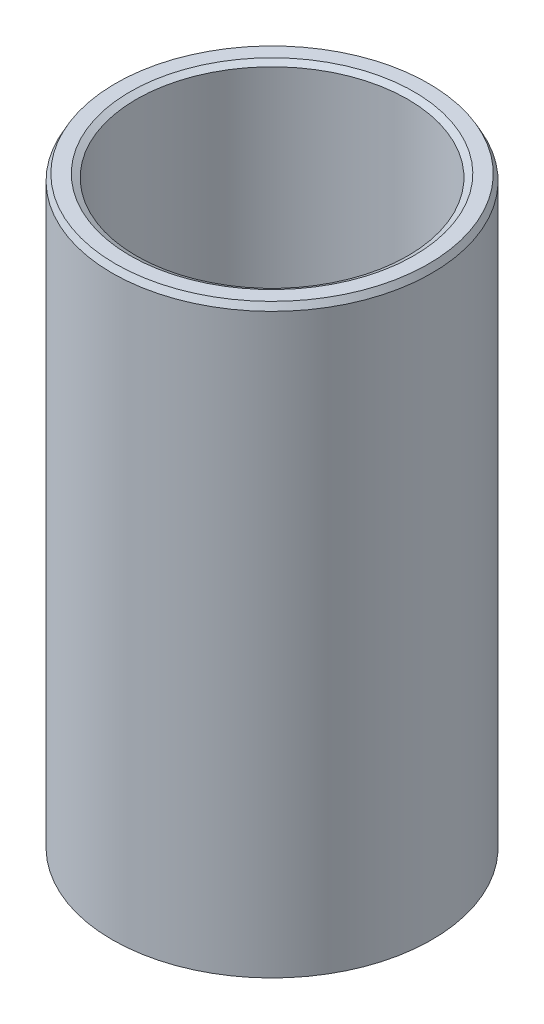
SolidWorks part; units mm, degrees
ref_plane "Front Plane" through (0, 0, 0) normal (0, 0, 1) x (1, 0, 0)
ref_plane "Top Plane" through (0, 0, 0) normal (0, 1, 0) x (1, 0, 0)
ref_plane "Right Plane" through (0, 0, 0) normal (1, 0, 0) x (0, 0, -1)
sketch "Sketch1" plane through (0, 0, 0) normal (0, 1, 0) x (1, 0, 0)
  circle A0 centre (0, 0) radius 50
  dimension "SLEEVE_OD" = 100
extrude "Boss-Extrude1" add sketch "Sketch1" along normal blind 183.6233
sketch "Sketch2" plane through (0, 0, 0) normal (0, 1, 0) x (1, 0, 0)
  circle A0 centre (0, 0) radius 42.4511
  dimension "BORE_D" = 84.9023
extrude "Cut-Extrude1" cut sketch "Sketch2" along normal through all
chamfer "Chamfer1" distance 1.9623 angle 28.374 4 edges at (0, 183.6233, 42.4511) (0, 0, 42.4511) (0, 0, 50) (0, 183.6233, 50) first distance on face at (0, 183.6233, 42.4511) first distance on face at (0, 0, 42.4511) first distance on face at (0, 183.6233, 50)
